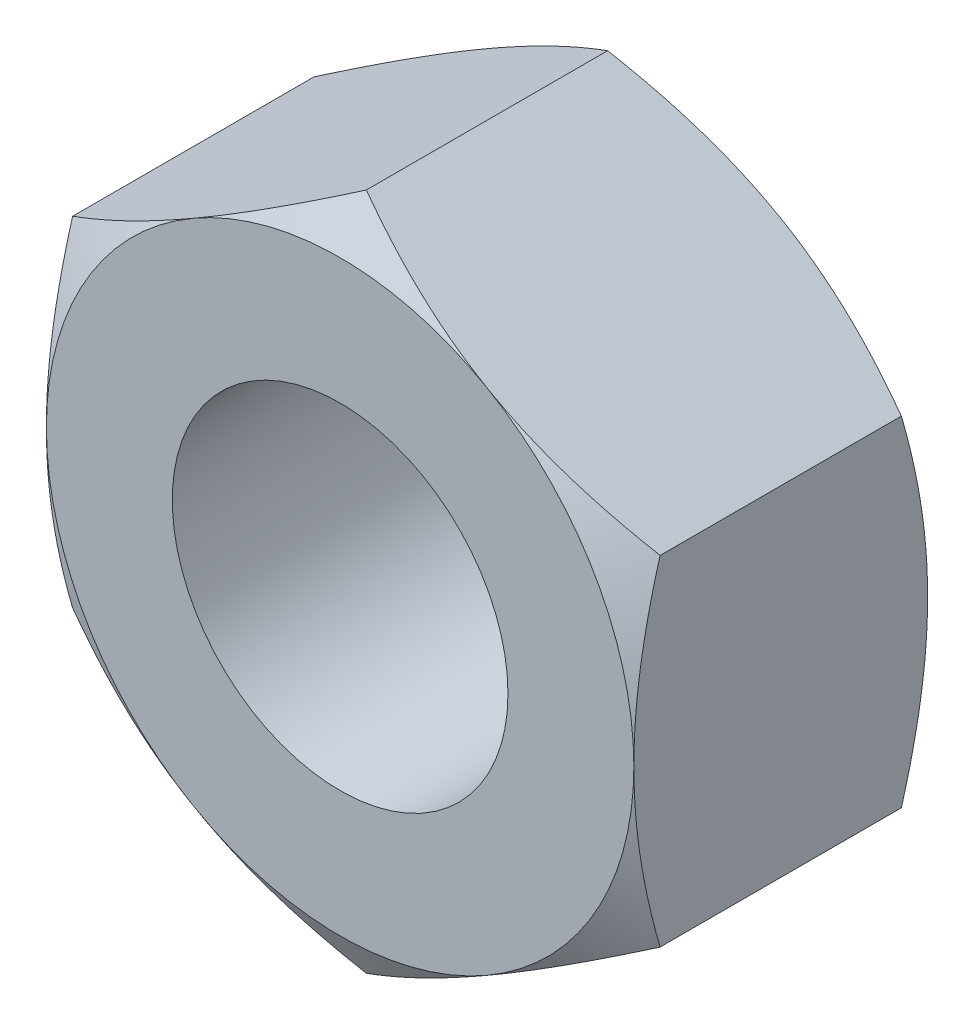
SolidWorks part; units mm, degrees
ref_plane "Front" through (0, 0, 0) normal (0, 0, 1) x (1, 0, 0)
ref_plane "Top" through (0, 0, 0) normal (0, 1, 0) x (1, 0, 0)
ref_plane "Right" through (0, 0, 0) normal (1, 0, 0) x (0, 0, -1)
sketch "Sketch1" plane through (0, 0, 0) normal (0, 0, 1) x (1, 0, 0)
  line L1 (-5.5562, 3.2079) -> (-5.5562, -3.2079)
  line L2 (-5.5562, -3.2079) -> (0, -6.4158)
  line L3 (0, -6.4158) -> (5.5562, -3.2079)
  line L4 (5.5562, -3.2079) -> (5.5562, 3.2079)
  line L5 (5.5562, 3.2079) -> (0, 6.4158)
  line L6 (0, 6.4158) -> (-5.5562, 3.2079)
  circle A0 centre (0, 0) radius 5.5562 construction
  circle A1 centre (0, 0) radius 3.175
  point P10 (0, 3.175)
  dimension "hex" = 11.1125
  dimension "dia" = 6.35
extrude "Extrude1" add sketch "Sketch1" along normal mid plane 5.5562
sketch "Sketch4" plane through (0, 0, -2.7781) normal (0, 0, -1) x (-1, 0, 0)
  circle A0 centre (0, 0) radius 3.175 construction
  circle A1 centre (0, 0) radius 3.175
curve "Helix/Spiral3" pitch 1.27 height 6.6675 turns 5.25
sketch "Sketch3" plane through (0, 0, 0) normal (1, 0, 0) x (0, 0, -1)
  line L0 (2.7781, 3.175) -> (3.8894, 3.175)
  line L1 (3.8894, 3.175) -> (3.4131, 2.3501)
  line L2 (3.4131, 2.3501) -> (3.2544, 2.3501)
  line L3 (3.2544, 2.3501) -> (2.7781, 3.175)
  line L4 (3.0163, 2.7626) -> (3.6513, 2.7626) construction
  dimension "D1" = 60
  dimension "D2" = 0.635
  dimension "D3" = 0.1588
sweep "Sweep1" [suppressed] add profiles "Sketch3" path "Helix/Spiral3"
sketch "Sketch6" [suppressed] plane through (0, 0, 0) normal (1, 0, 0) x (0, 0, -1)
  line L0 (-3.0956, 3.4925) -> (-2.4606, 2.8575)
  line L1 (-2.4606, 2.8575) -> (-2.4606, 0) construction
  line L2 (3.9291, 0) -> (-3.9291, 0) construction
  line L3 (-2.4606, 0) -> (-3.8894, 0)
  line L4 (-3.8894, 0) -> (-3.8894, 3.4925)
  line L5 (-3.8894, 3.4925) -> (-3.0956, 3.4925)
  line L6 (-2.4606, 2.8575) -> (0.3969, 0)
  line L7 (0.3969, 0) -> (-2.4606, 0)
  line L8 (-2.7781, -3.2079) -> (-2.7781, 3.2079) construction
  point P2 (-2.7781, 3.175)
  dimension "D2" = 0.635
  dimension "D1" = 45
revolve "Cut-Revolve1" [suppressed] cut sketch "Sketch6" angle 360 about L3
sketch "Sketch7" plane through (0, 0, 2.7781) normal (0, 0, 1) x (1, 0, 0)
  circle A0 centre (0, 0) radius 5.5562 construction
  circle A1 centre (0, 0) radius 5.5562
extrude "Extrude2" cut sketch "Sketch7" against normal blind 25.4 draft 60 flip side to cut
mirror "Mirror1" about plane through (0, 0, 0) normal (0, 0, 1) of "Extrude2", "Cut-Revolve1"
sketch "Sketch8" [suppressed] plane through (0, 0, 2.7781) normal (0, 0, 1) x (1, 0, 0)
  line L0 (-2.2451, 2.2451) -> (0, 0) construction
  line L1 (0, -3.9291) -> (0, 3.9291) construction
  circle A0 centre (0, 0) radius 3.175 construction
  point P0 (-2.2451, 2.2451)
  dimension "D1" = 45
equation "\"D3@Helix/Spiral3\" = \"length@Extrude1\" * 1.2"
equation "\"D2@Sketch3\" = \"D4@Helix/Spiral3\" * .5"
equation "\"D3@Sketch3\" = \"D4@Helix/Spiral3\" * .125"
equation "\"D2@Sketch6\" = \"D4@Helix/Spiral3\" * .5"
